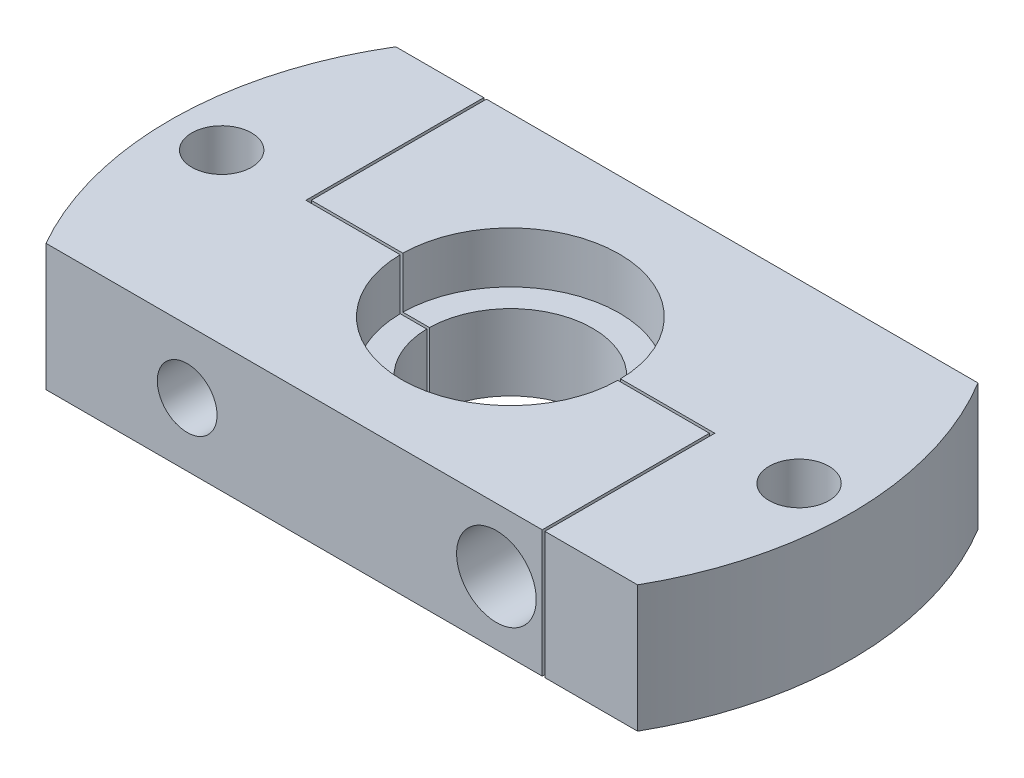
SolidWorks part; units mm, degrees
ref_plane "Front Plane" through (0, 0, 0) normal (0, 0, 1) x (1, 0, 0)
ref_plane "Top Plane" through (0, 0, 0) normal (0, 1, 0) x (1, 0, 0)
ref_plane "Right Plane" through (0, 0, 0) normal (1, 0, 0) x (0, 0, -1)
sketch "Sketch1" plane through (0, 0, 0) normal (0, 0, 1) x (1, 0, 0)
  line L0 (6.2, 58.45) -> (6.2, 52.75)
  line L3 (6.2, 58.45) -> (8.2, 58.45)
  line L4 (8.2, 58.45) -> (8.2, 62.3)
  line L11 (0, 0) -> (0, 50000) construction
  line L12 (6.2, 52.75) -> (25.65, 52.75)
  line L14 (25.65, 52.75) -> (25.65, 62.3)
  line L15 (25.65, 62.3) -> (8.2, 62.3)
  point P2 (0, 0)
  dimension "D1" = 5.7
  dimension "D2" = 2
  dimension "D3" = 3.85
  dimension "D4" = 17.45
  dimension "D6" = 52.75
  dimension "D7" = 6.2
revolve "Revolve1" add sketch "Sketch1" angle 360 about L11
sketch "Sketch2" plane through (0, 62.3, 0) normal (0, 1, 0) x (1, 0, 0)
  line L0 (-22.2853, -12.7) -> (22.2853, -12.7)
  line L1 (-15.2, 13.3) -> (-15.2, 0)
  line L3 (-15.2, 0) -> (15.2, 0)
  line L4 (-21.9325, 13.3) -> (21.9325, 13.3)
  line L5 (15.2, 0) -> (15.2, -12.7)
  line L6 (-15.3, 13.3) -> (-15.3, -0.1)
  line L7 (-15.3, -0.1) -> (15.1, -0.1)
  line L8 (15.1, -0.1) -> (15.1, -12.7)
  line L9 (-15.1, 13.3) -> (-15.1, 0.1)
  line L10 (-15.1, 0.1) -> (15.3, 0.1)
  line L11 (15.3, 0.1) -> (15.3, -12.7)
  circle A0 centre (0, 0) radius 25.65 construction
  circle A1 centre (0, 0) radius 8.2 construction
  point P18 (-8.2, 0)
  circle M4 centre (0, 0) radius 8.2
  circle M5 centre (0, 0) radius 25.65
  dimension "D3" = 7
  dimension "D1" = 12.7
  dimension "D2" = 13.3
  dimension "D4" = 0.1
  dimension "D5" = 0.1
extrude "Cut-Extrude1" cut sketch "Sketch2" against normal through all both and the other way through all contours L0 M5 | L4 M5 | L7 L3 M4 | L10 L3 M4 | L6 L7 L3 L1 L4 M4 | L10 L9 L4 L1 L3 M4 | L7 L8 L0 L5 L3 M4 | L11 L10 L3 L5 L0 M4 region at (0, 62.3, 18.0115) region at (15.1145, 62.3, 6.4) region at (0, 62.3, -18.3586) region at (15.2146, 62.3, 6.35) region at (-15.25, 62.3, -13.1483) region at (0, 62.3, 0.05) region at (-15.15, 62.3, -13.1497) region at (0, 62.3, -0.05)
hole_wizard "CBORE for M3 Hex Socket Head Cap Screw3" positions "Sketch8" profile "Sketch9" counterbore size "M3" standard "DIN" end condition through all
sketch "Sketch8" plane through (0, 0, -13.3) normal (0, 0, -1) x (-1, 0, 0)
  line L0 (15.1, 52.75) -> (-21.9325, 52.75) construction
  line L1 (15.1, 62.3) -> (8.1994, 62.3) construction
  line L2 (15.1, 52.75) -> (-21.9325, 52.75) construction
  line L3 (15.1, 62.3) -> (8.1994, 62.3) construction
  line L4 (11.6497, 62.3) -> (11.6497, 52.75) construction
  point P8 (11.6497, 57.525)
  point P11 (0, 0)
sketch "Sketch9" plane through (-11.6497, 57.525, -13.3) normal (1, 0, 0) x (0, 1, 0)
  line L0 (0, 0) -> (0, 26.0003)
  line L1 (0, 26.0003) -> (1.7, 26.0003)
  line L3 (1.7, 26.0003) -> (1.7, 9.4)
  line L4 (1.7, 9.4) -> (3, 9.4)
  line L5 (3, 9.4) -> (3, 0)
  line L7 (3, 0) -> (0, 0)
  line L11 (0, -6.35) -> (0, 107.95) construction
  dimension "Thru Hole Dia." = 3.4
  dimension "Thru Hole Depth" = 26.0003
  dimension "C'Bore Dia." = 6
  dimension "C'Bore Depth" = 9.4
hole_wizard "CBORE for M3 Hex Socket Head Cap Screw4" positions "Sketch12" profile "Sketch13" counterbore size "M3" standard "DIN" end condition through all
sketch "Sketch12" plane through (0, 0, 12.7) normal (0, 0, 1) x (1, 0, 0)
  line L0 (-22.2853, 52.75) -> (15.1, 52.75) construction
  line L1 (8.1994, 62.3) -> (15.1, 62.3) construction
  line L2 (-22.2853, 52.75) -> (15.1, 52.75) construction
  line L3 (8.1994, 62.3) -> (15.1, 62.3) construction
  line L4 (11.6497, 62.3) -> (11.6497, 52.75) construction
  point P9 (11.6497, 57.525)
sketch "Sketch13" plane through (11.6497, 57.525, 12.7) normal (1, 0, 0) x (0, -1, 0)
  line L0 (0, 0) -> (0, 26.0003)
  line L1 (0, 26.0003) -> (1.7, 26.0003)
  line L3 (1.7, 26.0003) -> (1.7, 9.4)
  line L4 (1.7, 9.4) -> (3, 9.4)
  line L5 (3, 9.4) -> (3, 0)
  line L7 (3, 0) -> (0, 0)
  line L11 (0, -6.35) -> (0, 107.95) construction
  dimension "Thru Hole Dia." = 3.4
  dimension "Thru Hole Depth" = 26.0003
  dimension "C'Bore Dia." = 6
  dimension "C'Bore Depth" = 9.4
sketch "Sketch14" plane through (0, 0, 12.7) normal (0, 0, 1) x (1, 0, 0)
  circle A0 centre (11.6497, 57.525) radius 1.7 construction
  circle A1 centre (-11.6497, 57.525) radius 1.7 construction
  circle A2 centre (11.6497, 57.525) radius 1.7 construction
  circle A3 centre (-11.6497, 57.525) radius 1.7 construction
  circle A4 centre (-11.6497, 57.525) radius 2.25
  circle A5 centre (11.6497, 57.525) radius 2.25
  dimension "D1" = 4.5
extrude "Cut-Extrude4" cut sketch "Sketch14" against normal blind 4.25 contours A4
extrude "Cut-Extrude5" cut sketch "Sketch14<3>" along normal blind 4.25 from surface contours A5 starting at face at (13.3497, 57.525, -13.3)
sketch "Sketch14<3>" plane through (0, 0, 12.7) normal (0, 0, 1) x (1, 0, 0) same geometry as "Sketch14"
sketch "Sketch15" plane through (0, 62.3, 0) normal (0, 1, 0) x (1, 0, 0)
  line L0 (0, 0) -> (0, 50000) construction
  circle A1 centre (-21.75, 0) radius 2.25
  circle A2 centre (21.75, 0) radius 2.25
  point P1 (0, 0)
  dimension "D1" = 21.75
  dimension "D2" = 4.5
extrude "Cut-Extrude6" cut sketch "Sketch15" against normal blind 5
